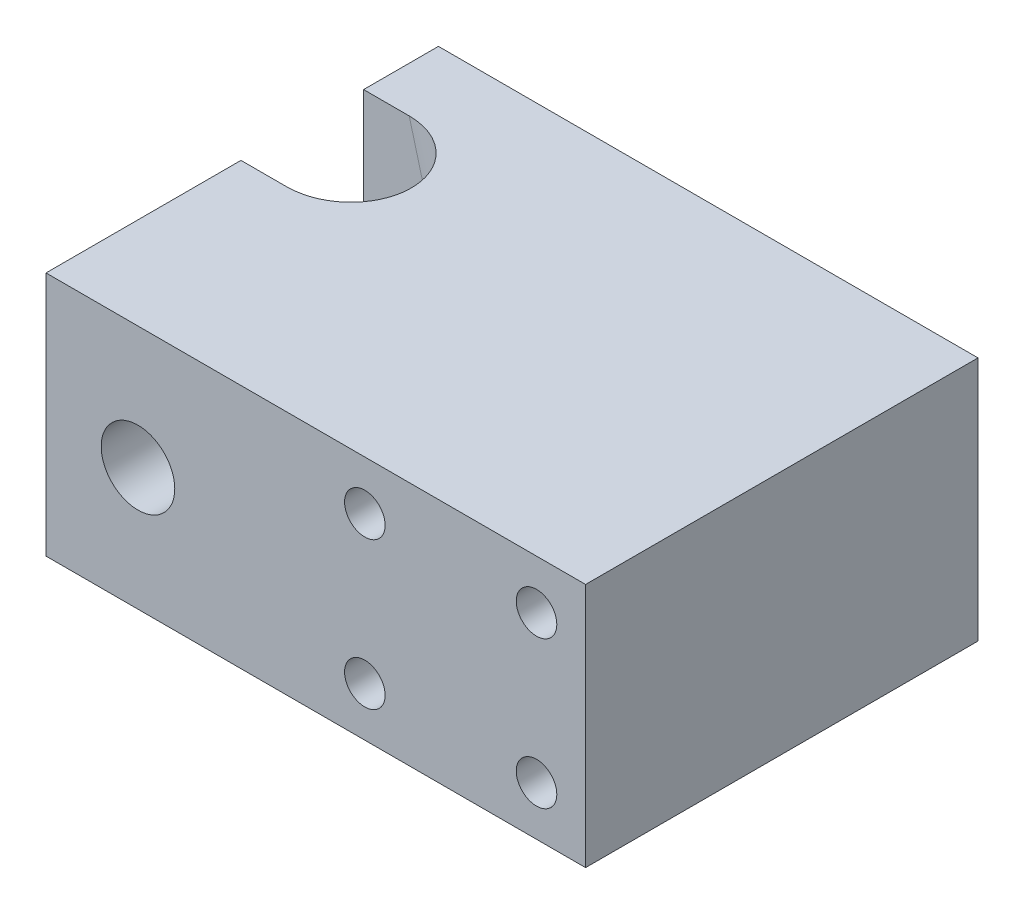
SolidWorks part; units mm, degrees
ref_plane "Front Plane" through (0, 0, 0) normal (0, 0, 1) x (1, 0, 0)
ref_plane "Top Plane" through (0, 0, 0) normal (0, 1, 0) x (1, 0, 0)
ref_plane "Right Plane" through (0, 0, 0) normal (1, 0, 0) x (0, 0, -1)
sketch "Sketch1" plane through (0, 0, 0) normal (0, 1, 0) x (1, 0, 0)
  line L1 (0, 0) -> (55.88, 0)
  line L2 (0, 0) -> (0, 40.64)
  line L3 (0, 40.64) -> (55.88, 40.64)
  line L4 (55.88, 0) -> (55.88, 40.64)
  dimension "D1" = 40.64
  dimension "D2" = 55.88
extrude "Boss-Extrude1" add sketch "Sketch1" along normal blind 25.4
sketch "Sketch3" plane through (0, 0, 0) normal (0, 0, 1) x (1, 0, 0)
  line L0 (0, 25.4) -> (0, 0) construction
  line L1 (0, 25.4) -> (55.88, 25.4) construction
  circle A0 centre (9.525, 12.7) radius 3.81
  dimension "D1" = 7.62
  dimension "D2" = 9.525
  dimension "D3" = 12.7
extrude "Cut-Extrude1" cut sketch "Sketch3" against normal through all
sketch "Sketch4" plane through (0, 25.4, 0) normal (0, 1, 0) x (1, 0, 0)
  line L0 (0, 40.64) -> (0, 0) construction
  line L1 (17.78, 31.3025) -> (0, 31.3025)
  line L2 (17.78, 31.3025) -> (17.78, 21.7775)
  line L3 (17.78, 21.7775) -> (0, 21.7775)
  line L4 (0, 31.3025) -> (0, 21.7775)
  line L5 (17.78, 31.3025) -> (0, 21.7775) construction
  line L6 (17.78, 21.7775) -> (0, 31.3025) construction
  line L7 (55.88, 40.64) -> (0, 40.64) construction
  point P0 (8.89, 26.54)
  dimension "D1" = 14.1
  dimension "D2" = 9.525
  dimension "D3" = 17.78
extrude "Cut-Extrude2" [suppressed] cut sketch "Sketch4" against normal through all
hole_wizard "M5x0.8 Tapped Hole1" positions "Sketch7" profile "Sketch6" tap size "M5x0.8" standard "ANSI Metric"
sketch "Sketch7" plane through (0, 0, 0) normal (0, 0, 1) x (1, 0, 0)
  line L0 (0, 0) -> (55.88, 0) construction
  line L1 (55.88, 25.4) -> (55.88, 0) construction
  point P0 (50.8, 5.08)
  point P11 (33.02, 5.08)
  point P12 (33.02, 20.32)
  point P13 (50.8, 20.32)
  dimension "D1" = 5.08
  dimension "D2" = 5.08
  dimension "D3" = 2
  dimension "D4" = 2
sketch "Sketch6" plane through (50.8, 5.08, 0) normal (1, 0, 0) x (0, -1, 0)
  line L0 (0, 0) -> (0, 26.6618)
  line L1 (0, 26.6618) -> (2.1, 25.4)
  line L2 (2.1, 25.4) -> (2.1, 0)
  line L5 (2.1, 0) -> (0, 0)
  line L10 (0, 26.6618) -> (-2.1, 25.4) construction
  line L11 (0, -6.35) -> (0, 107.95) construction
  dimension "Tap Drill Dia." = 4.2
  dimension "Tap Drill Depth" = 25.4
  dimension "Drill Angle" = 118
cosmetic thread "Hole Thread1" parameters "D1"=20.32, "D2"=5
cosmetic thread "Hole Thread2" parameters "D1"=20.32, "D2"=5
cosmetic thread "Hole Thread3" parameters "D1"=20.32, "D2"=5
cosmetic thread "Hole Thread4" parameters "D1"=20.32, "D2"=5
ref_axis "Axis1" through (9.525, 12.7, -40.64) along (0, 0, 1)
ref_plane "Plane1" through (-2.5369, 9.468, 0) normal (-0.2588, 0.9659, 0) x (0.9659, 0.2588, 0)
sketch "Sketch8" plane through (-2.5369, 9.468, 0) normal (-0.2588, 0.9659, 0) x (0.9659, 0.2588, 0)
  line L1 (60.5499, 40.64) -> (6.574, 40.64) construction
  line L2 (12.4874, 40.64) -> (12.4874, 0) construction
  line L4 (11.1374, 32.89) -> (0, 32.89)
  line L5 (11.1374, 32.89) -> (11.1374, 20.19)
  line L6 (11.1374, 20.19) -> (0, 20.19)
  line L7 (0, 32.89) -> (0, 20.19)
  circle A0 centre (11.1374, 26.54) radius 6.35
  dimension "D1" = 12.7
  dimension "D2" = 14.1
  dimension "D3" = 1.35
extrude "Cut-Extrude3" cut sketch "Sketch8" against normal through all and the other way through all contours A0 L4 L7 L6 | L5 A0 L6 | L6 A0 L5 region at (0.5911, 10.3062, -26.54) region at (10.8242, 13.0481, -26.54) region at (5.6178, 11.6531, -26.54)
